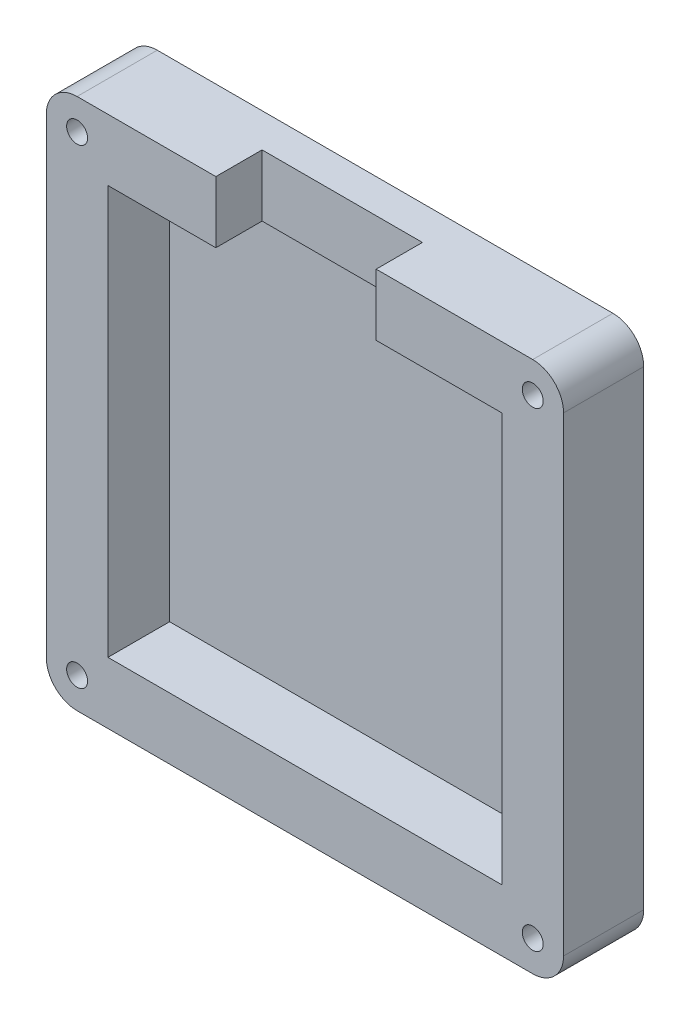
SolidWorks part; units mm, degrees
ref_plane "Front Plane" through (0, 0, 0) normal (0, 0, 1) x (1, 0, 0)
ref_plane "Top Plane" through (0, 0, 0) normal (0, 1, 0) x (1, 0, 0)
ref_plane "Right Plane" through (0, 0, 0) normal (1, 0, 0) x (0, 0, -1)
sketch "Sketch2" plane through (0, 0, 0) normal (0, 0, 1) x (1, 0, 0)
  line L1 (31.9465, 33.1375) -> (-31.9465, 33.1375)
  line L2 (31.9465, 33.1375) -> (31.9465, -33.1375)
  line L3 (31.9465, -33.1375) -> (-31.9465, -33.1375)
  line L4 (-31.9465, 33.1375) -> (-31.9465, -33.1375)
  line L5 (31.9465, 33.1375) -> (-31.9465, -33.1375) construction
  line L6 (31.9465, -33.1375) -> (-31.9465, 33.1375) construction
  line L7 (-41.9465, 43.1375) -> (41.9465, 43.1375)
  line L8 (-41.9465, 43.1375) -> (-41.9465, -43.1375)
  line L9 (-41.9465, -43.1375) -> (41.9465, -43.1375)
  line L10 (41.9465, 43.1375) -> (41.9465, -43.1375)
  circle A5 centre (36.9465, 38.1375) radius 1.7
  circle A6 centre (-36.9465, -38.1375) radius 1.7
  circle A7 centre (36.9465, -38.1375) radius 1.7
  circle A8 centre (-36.9465, 38.1375) radius 1.7
  circle A9 centre (-36.9465, 38.1375) radius 3.25
  circle A10 centre (36.9465, 38.1375) radius 3.25
  circle A11 centre (-36.9465, -38.1375) radius 3.25
  circle A12 centre (36.9465, -38.1375) radius 3.25
  point P0 (0, 0)
  dimension "D8" = 5
  dimension "D9" = 3.4
  dimension "D10" = 5
  dimension "D12" = 3.4
  dimension "D13" = 3.4
  dimension "D14" = 5
  dimension "D15" = 5
  dimension "D16" = 3.4
  dimension "D17" = 5
  dimension "D18" = 5
  dimension "D19" = 6.5
  dimension "D20" = 6.5
  dimension "D21" = 6.5
  dimension "D22" = 6.5
  dimension "D1" = 63.893
  dimension "D2" = 66.275
  dimension "D3" = 10
  dimension "D4" = 10
  dimension "D5" = 10
  dimension "D6" = 10
  dimension "D7" = 5
  dimension "D11" = 5
  dimension "D23" = 83.893
  dimension "D24" = 86.275
extrude "Boss-Extrude4" add sketch "Sketch2" along normal blind 9.9 from offset 3.1 contours A5 | A10 | A9 | A6 | A11 | A7 | A12 | A8
extrude "Boss-Extrude5" add sketch "Sketch2<12>" along normal blind 13 contours L10 L7 L8 L9 A12 A11 A10 A9 L4 L1 L2 L3 region at (0, 41.9341, 0)
sketch "Sketch2<12>" plane through (0, 0, 0) normal (0, 0, 1) x (1, 0, 0) same geometry as "Sketch2"
extrude "Boss-Extrude6" add sketch "Sketch2<13>" along normal blind 3 contours L1 L4 L3 L2 region at (0, 0, 0)
sketch "Sketch2<13>" plane through (0, 0, 0) normal (0, 0, 1) x (1, 0, 0) same geometry as "Sketch2"
sketch "Sketch5" plane through (0, 0, 13) normal (0, 0, 1) x (1, 0, 0)
  line L0 (-41.9465, 43.1375) -> (41.9465, 43.1375) construction
  line L1 (-14.4465, 43.1375) -> (11.5535, 43.1375)
  line L2 (-14.4465, 43.1375) -> (-14.4465, 33.1375)
  line L3 (-14.4465, 33.1375) -> (11.5535, 33.1375)
  line L4 (11.5535, 43.1375) -> (11.5535, 33.1375)
  line L5 (31.9465, 33.1375) -> (-31.9465, 33.1375) construction
  line L6 (-31.9465, 33.1375) -> (-31.9465, -33.1375) construction
  dimension "D1" = 26
  dimension "D2" = 17.5
extrude "Cut-Extrude1" cut sketch "Sketch5" against normal blind 7.5 contours L2 L3 L4 L1
fillet "Fillet1" radius 5 4 edges at (-41.9465, -43.1375, 6.5) (-41.9465, 43.1375, 6.5) (41.9465, -43.1375, 6.5) (41.9465, 43.1375, 6.5)
sketch "Sketch7" plane through (0, 0, 0) normal (0, 0, -1) x (-1, 0, 0)
  text T0 "darsh's tetrios" font "Century Gothic" height in points 8
  dimension "D1" = 0
extrude "Cut-Extrude2" cut sketch "Sketch7" against normal blind 0.2
